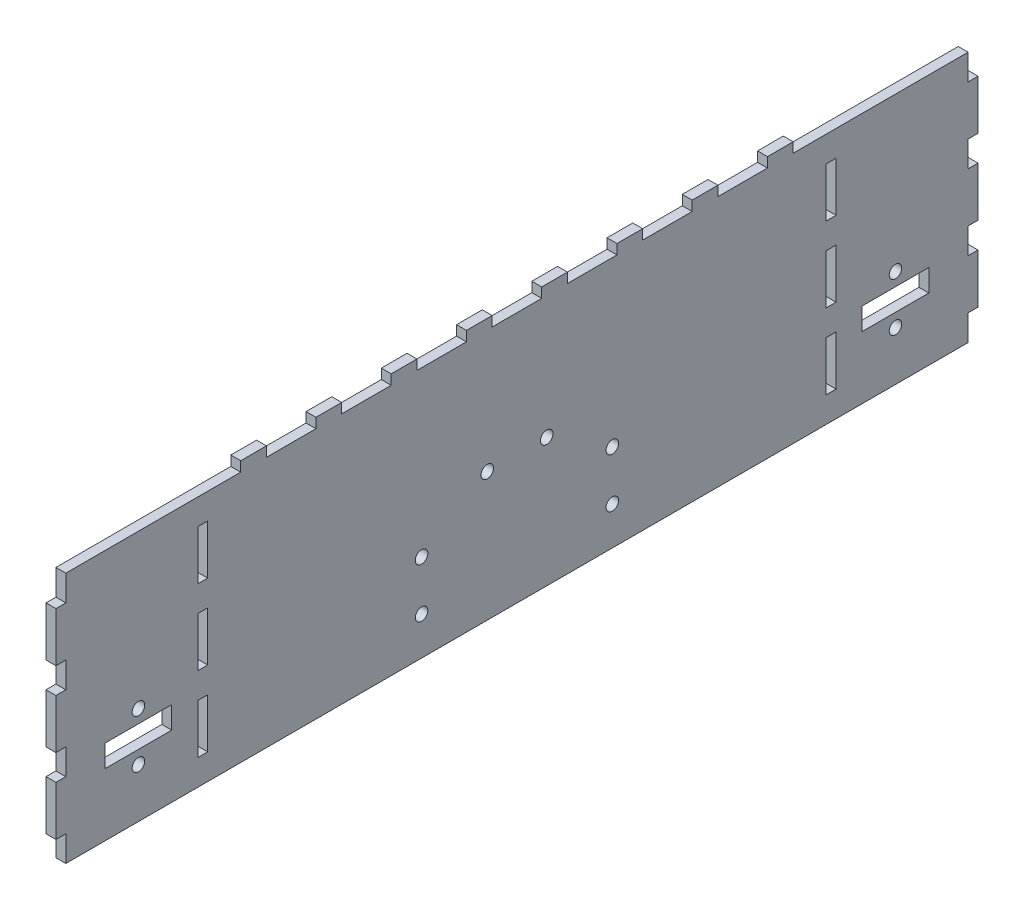
SolidWorks part; units mm, degrees
material "ENPH 253 Hardboard"
ref_plane "Front Plane" through (0, 0, 0) normal (0, 0, 1) x (1, 0, 0)
ref_plane "Top Plane" through (0, 0, 0) normal (0, 1, 0) x (1, 0, 0)
ref_plane "Right Plane" through (0, 0, 0) normal (1, 0, 0) x (0, 0, -1)
sketch "Sketch1" plane through (0, 0, 0) normal (1, 0, 0) x (0, 0, -1)
  line L1 (-139.7, 38.1) -> (139.7, 38.1)
  line L2 (-139.7, 38.1) -> (-139.7, -38.1)
  line L3 (-139.7, -38.1) -> (139.7, -38.1)
  line L4 (139.7, 38.1) -> (139.7, -38.1)
  line L5 (-139.7, 38.1) -> (139.7, -38.1) construction
  line L6 (-139.7, -38.1) -> (139.7, 38.1) construction
  point P0 (0, 0)
  dimension "D1" = 279.4
  dimension "D2" = 76.2
extrude "Boss-Extrude1" add sketch "Sketch1" against normal blind 3 contours L2 L3 L4 L1
sketch "Sketch3" plane through (-3, 0, 0) normal (-1, 0, 0) x (0, 0, 1)
  line L9 (-139.7, 38.1) -> (-136.7, 38.1)
  line L10 (-139.7, 38.1) -> (-139.7, 30.3)
  line L11 (-139.7, 30.3) -> (-136.7, 30.3)
  line L12 (-136.7, 38.1) -> (-136.7, 30.3)
  dimension "D9" = 7.8
  dimension "D10" = 3
extrude "Cut-Extrude1" cut sketch "Sketch3" against normal through all
pattern_linear "LPattern1" count 4 spacing 22.8 along (0, -1, 0) of "Cut-Extrude1"
mirror "Mirror1" about plane through (0, 0, 0) normal (0, 0, 1) of "LPattern1"
sketch "Sketch4" plane through (0, 0, 0) normal (1, 0, 0) x (0, 0, -1)
  line L1 (-96.7, 30.3) -> (-93.7, 30.3)
  line L2 (-96.7, 30.3) -> (-96.7, 15.3)
  line L3 (-96.7, 15.3) -> (-93.7, 15.3)
  line L4 (-93.7, 30.3) -> (-93.7, 15.3)
  line L5 (-136.7, 38.1) -> (136.7, 38.1) construction
  line L6 (-136.7, 30.3) -> (-136.7, 38.1) construction
  dimension "D1" = 40
  dimension "D2" = 3
  dimension "D3" = 7.8
  dimension "D4" = 15
extrude "Cut-Extrude2" cut sketch "Sketch4" against normal blind 10
pattern_linear "LPattern2" count 3 spacing 22.8 along (0, -1, 0) of "Cut-Extrude2"
mirror "Mirror2" about plane through (0, 0, 0) normal (0, 0, 1) of "LPattern2"
sketch "Sketch5" plane through (0, 38.1, 0) normal (0, 1, 0) x (1, 0, 0)
  line L0 (-3, -136.7) -> (-3, 136.7) construction
  line L1 (-3, -75.9) -> (0, -75.9)
  line L2 (-3, -75.9) -> (-3, -83.7)
  line L3 (-3, -83.7) -> (0, -83.7)
  line L4 (0, -75.9) -> (0, -83.7)
  line L5 (0, -136.7) -> (-3, -136.7) construction
  dimension "D1" = 53
  dimension "D2" = 7.8
  dimension "D3" = 3
extrude "Boss-Extrude2" add sketch "Sketch5" along normal blind 3
pattern_linear "LPattern3" count 8 spacing 22.8 along (0, 0, -1) of "Boss-Extrude2"
hole_wizard "#6 Clearance Hole1" positions "Sketch6" profile "Sketch7" hole size "#6" standard "ANSI Inch" end condition up to next
sketch "Sketch6" plane through (-3, 0, 0) normal (-1, 0, 0) x (0, 0, 1)
  point P0 (-28.9, -11.55)
  point P3 (-28.9, -26.55)
  point P6 (28.9, -26.55)
  point P9 (28.9, -11.55)
sketch "Sketch7" plane through (-3, -11.55, -28.9) normal (0, 1, 0) x (0, 0, 1)
  line L0 (0, 0) -> (0, 3)
  line L1 (0, 3) -> (1.8986, 3)
  line L2 (1.8986, 3) -> (1.8986, 0)
  line L5 (1.8986, 0) -> (0, 0)
  line L11 (0, -6.35) -> (0, 107.95) construction
  dimension "Thru Hole Dia." = 3.7973
  dimension "Thru Hole Depth" = 3
hole_wizard "#6 Clearance Hole2" positions "Sketch8" profile "Sketch9" hole size "#6" standard "ANSI Inch" end condition through all
sketch "Sketch8" plane through (0, 0, 0) normal (1, 0, 0) x (0, 0, -1)
  point P0 (-9, 0.9)
  point P3 (9, 0.9)
sketch "Sketch9" plane through (0, 0.9, 9) normal (0, 1, 0) x (0, 0, -1)
  line L0 (0, 0) -> (0, 3)
  line L1 (0, 3) -> (1.8986, 3)
  line L2 (1.8986, 3) -> (1.8986, 0)
  line L5 (1.8986, 0) -> (0, 0)
  line L11 (0, -6.35) -> (0, 107.95) construction
  dimension "Thru Hole Dia." = 3.7973
  dimension "Thru Hole Depth" = 3
sketch "Sketch10" plane through (-3, 0, 0) normal (-1, 0, 0) x (0, 0, 1)
  line L0 (136.7, -38.1) -> (-136.7, -38.1) construction
  line L5 (124.7, -19.05) -> (104.7, -19.05) construction
  line L6 (124.7, -19.05) -> (124.7, -12.55) construction
  line L7 (124.7, -12.55) -> (104.7, -12.55) construction
  line L8 (104.7, -19.05) -> (104.7, -12.55) construction
  line L9 (139.7, -15.3) -> (139.7, -30.3) construction
  line L10 (124.8, -19.15) -> (124.8, -12.45)
  line L11 (124.8, -12.45) -> (104.6, -12.45)
  line L12 (104.6, -19.15) -> (104.6, -12.45)
  line L13 (124.8, -19.15) -> (104.6, -19.15)
  line L14 (0, 38.1) -> (0, -39.0089) construction
  line L15 (7.5, 38.1) -> (-7.5, 38.1) construction
  line L16 (-124.8, -19.15) -> (-104.6, -19.15)
  line L17 (-104.6, -19.15) -> (-104.6, -12.45)
  line L18 (-124.8, -12.45) -> (-104.6, -12.45)
  line L19 (-124.8, -19.15) -> (-124.8, -12.45)
  dimension "D1" = 19.05
  dimension "D2" = 15
  dimension "D3" = 20
  dimension "D4" = 6.5
  dimension "D5" = 0.1
extrude "Cut-Extrude3" cut sketch "Sketch10" against normal up to next
hole_wizard "#6 Clearance Hole3" positions "Sketch11" profile "Sketch12" hole size "#6" standard "ANSI Inch" end condition through all
sketch "Sketch11" plane through (-3, 0, 0) normal (-1, 0, 0) x (0, 0, 1)
  line L0 (-124.8, -15.8) -> (-104.6, -15.8) construction
  line L1 (-124.8, -12.45) -> (-124.8, -19.15) construction
  line L2 (-104.6, -19.15) -> (-104.6, -12.45) construction
  line L4 (0, 0) -> (0, -38.1) construction
  line L5 (136.7, -38.1) -> (-136.7, -38.1) construction
  line L7 (-104.6, -12.45) -> (-124.8, -12.45) construction
  point P0 (-114.7, -8.45)
  point P16 (0, 0)
  point P18 (-114.7, -15.8)
  point P21 (-114.7, -23.15)
  point P22 (0, 0)
  point P23 (114.7, -23.15)
  point P24 (114.7, -8.45)
  dimension "D1" = 4
sketch "Sketch12" plane through (-3, -8.45, -114.7) normal (0, 1, 0) x (0, 0, 1)
  line L0 (0, 0) -> (0, 3)
  line L1 (0, 3) -> (1.8986, 3)
  line L2 (1.8986, 3) -> (1.8986, 0)
  line L5 (1.8986, 0) -> (0, 0)
  line L11 (0, -6.35) -> (0, 107.95) construction
  dimension "Thru Hole Dia." = 3.7973
  dimension "Thru Hole Depth" = 3
